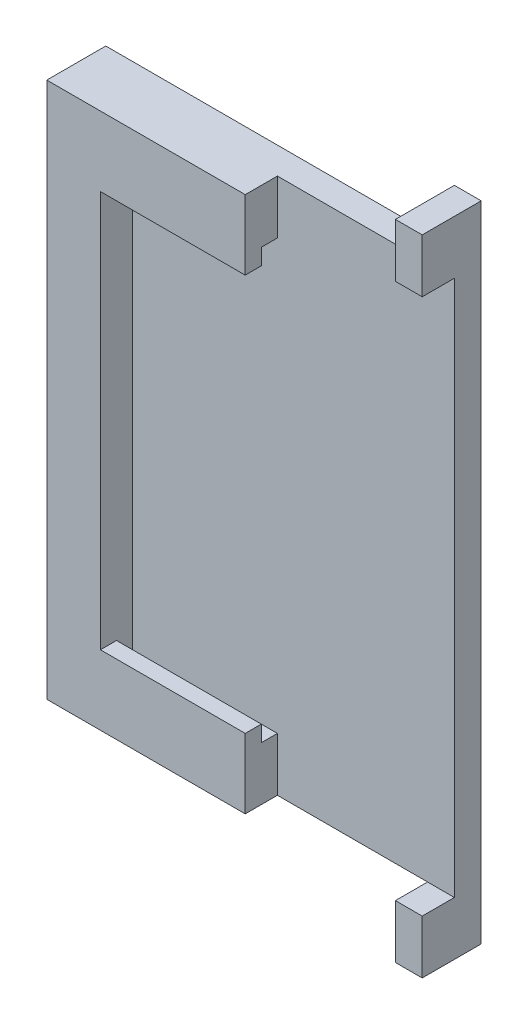
SolidWorks part; units mm, degrees
ref_plane "Front Plane" through (0, 0, 0) normal (1, 0, 0) x (0, 1, 0)
ref_plane "Top Plane" through (0, 0, 0) normal (0, 0, 1) x (0, 1, 0)
ref_plane "Right Plane" through (0, 0, 0) normal (0, 1, 0) x (-1, 0, 0)
sketch "Sketch1" plane through (0, 0, 0) normal (0, 0, 1) x (0, 1, 0)
  line L2 (-50, 5) -> (-50, 70)
  line L3 (-50, 70) -> (50, 70)
  line L4 (50, 5) -> (50, 70)
  line L5 (-60, 0) -> (-60, 5)
  line L6 (-60, 5) -> (-50, 5)
  line L7 (0, 70) -> (0, 0) construction
  line L9 (60, 0) -> (60, 5)
  line L10 (60, 5) -> (50, 5)
  line L11 (-60, 0) -> (60, 0)
  point P0 (49.9179, 10)
  dimension "D1" = 100
  dimension "D2" = 10
  dimension "D3" = 5
  dimension "D4" = 70
extrude "Boss-Extrude1" add sketch "Sketch1" along normal blind 5
sketch "Sketch4" plane through (0, 0, 5) normal (0, 0, 1) x (1, 0, 0)
  line L0 (-70, 50) -> (-70, -50)
  line L1 (-5, 50) -> (0, 50)
  line L2 (-5, 50) -> (-5, 60)
  line L3 (-5, 60) -> (0, 60)
  line L4 (0, 50) -> (0, 60)
  line L5 (-5, -50) -> (0, -50)
  line L6 (-5, -50) -> (-5, -60)
  line L7 (-5, -60) -> (0, -60)
  line L8 (0, -50) -> (0, -60)
  line L9 (-70, 50) -> (-33, 50)
  line L11 (-60, 40) -> (-33, 40)
  line L12 (-33, 50) -> (-33, 40)
  line L13 (-70, -50) -> (-33, -50)
  line L15 (-60, -40) -> (-33, -40)
  line L16 (-33, -50) -> (-33, -40)
  line L17 (-60, 40) -> (-60, -40)
  dimension "D1" = 10
  dimension "D2" = 27
  dimension "D3" = 10
  dimension "D4" = 10
extrude "Boss-Extrude2" add sketch "Sketch4" along normal blind 6
sketch "Sketch5" plane through (-60, 0, 0) normal (1, 0, 0) x (0, 1, 0)
  line L0 (0, 11) -> (0, 5) construction
  line L1 (-40, 11) -> (-37, 11)
  line L2 (-40, 11) -> (-40, 8)
  line L3 (-40, 8) -> (-37, 8)
  line L4 (-37, 11) -> (-37, 8)
  line L5 (-40, 11) -> (40, 11) construction
  line L6 (-40, 5) -> (40, 5) construction
  line L7 (40, 8) -> (37, 8)
  line L8 (37, 11) -> (37, 8)
  line L9 (40, 11) -> (37, 11)
  line L10 (40, 11) -> (40, 8)
  dimension "D1" = 3
  dimension "D2" = 3
extrude "Boss-Extrude3" add sketch "Sketch5" along normal up to surface (27 mm away) up to face at (-33, -45, 8)
